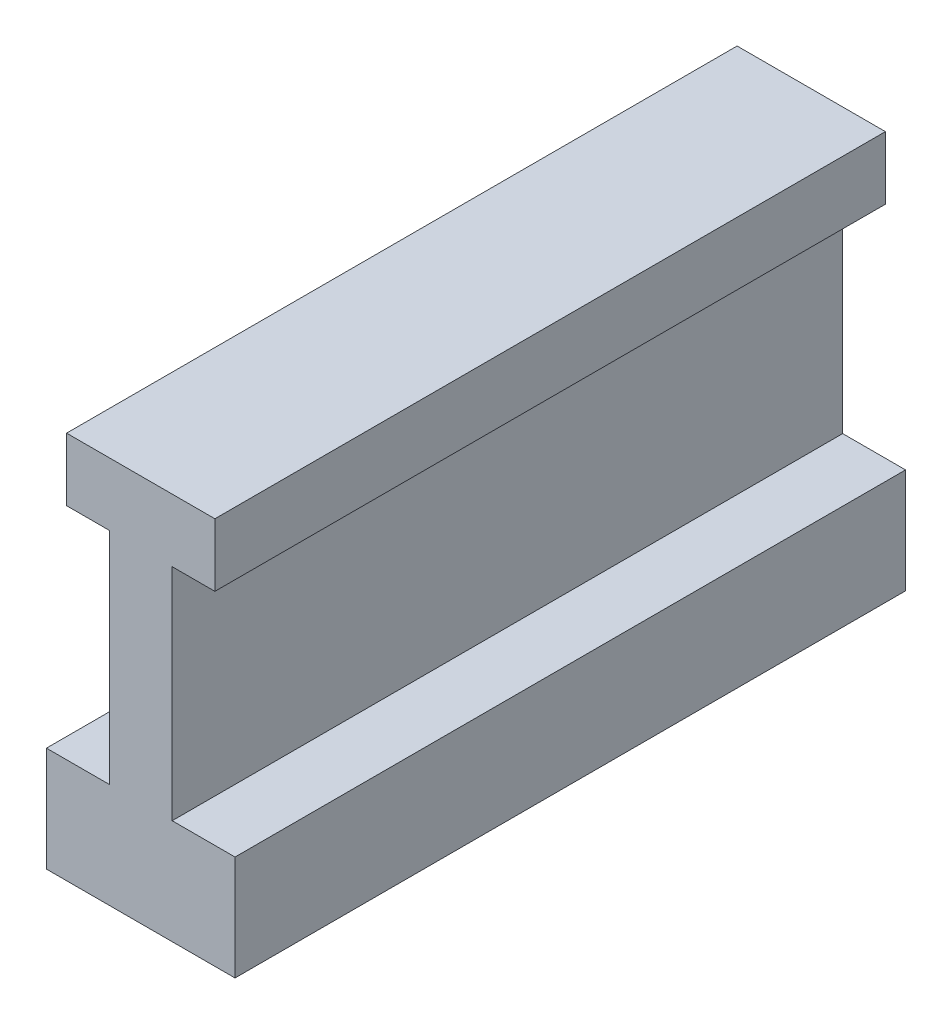
SolidWorks part; units mm, degrees
ref_plane "Front Plane" through (0, 0, 0) normal (0, 0, 1) x (1, 0, 0)
ref_plane "Top Plane" through (0, 0, 0) normal (0, 1, 0) x (1, 0, 0)
ref_plane "Right Plane" through (0, 0, 0) normal (1, 0, 0) x (0, 0, -1)
sketch "Sketch2" plane through (0, 0, 0) normal (0, 0, 1) x (1, 0, 0)
  line L0 (0, 0) -> (0, 10)
  line L1 (0, 10) -> (6, 10)
  line L2 (6, 10) -> (6, 31)
  line L3 (6, 31) -> (1.9223, 31)
  line L4 (1.9223, 31) -> (1.9223, 37)
  line L5 (1.9223, 37) -> (16.0777, 37)
  line L6 (16.0777, 37) -> (16.0777, 31)
  line L7 (16.0777, 31) -> (12, 31)
  line L8 (12, 31) -> (12, 10)
  line L9 (12, 10) -> (18, 10)
  line L10 (18, 10) -> (18, 0)
  line L11 (18, 0) -> (0, 0)
  line L12 (9, 0) -> (9, 37) construction
  point P15 (0, 0)
  point P16 (9, 37)
  dimension "D1" = 18
  dimension "D2" = 6
  dimension "D3" = 6
  dimension "D4" = 10
  dimension "D5" = 21
extrude "Boss-Extrude2" add sketch "Sketch2" along normal blind 64
